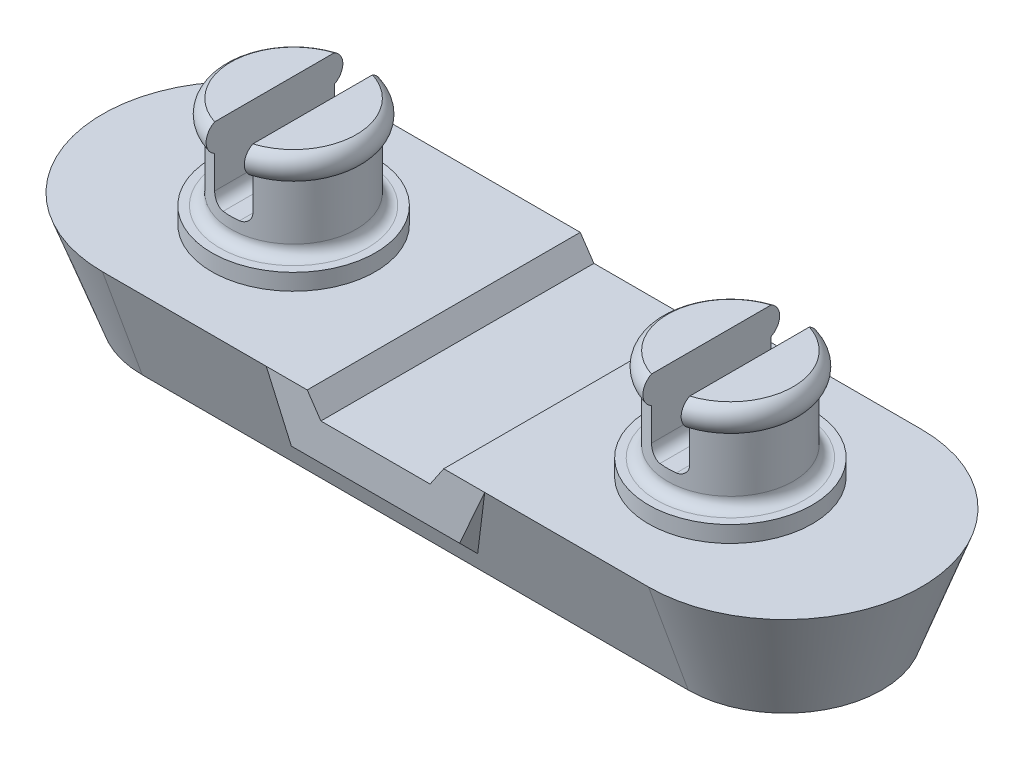
SolidWorks part; units mm, degrees
ref_plane "Front Plane" through (0, 0, 0) normal (0, 0, 1) x (1, 0, 0)
ref_plane "Top Plane" through (0, 0, 0) normal (0, 1, 0) x (1, 0, 0)
ref_plane "Right Plane" through (0, 0, 0) normal (1, 0, 0) x (0, 0, -1)
sketch "Sketch1" plane through (0, 0, 0) normal (0, 1, 0) x (1, 0, 0)
  line L0 (-10, 0) -> (10, 0) construction
  line L1 (-10, 5) -> (10, 5)
  line L2 (-10, -5) -> (10, -5)
  arc A0 (-10, 5) -> (-10, -5) centre (-10, 0) ccw
  arc A1 (10, -5) -> (10, 5) centre (10, 0) ccw
  point P3 (0, 0)
  point P8 (0, 0)
  point P9 (0, 0)
  dimension "D1" = 20
  dimension "D2" = 10
extrude "Boss-Extrude1" add sketch "Sketch1" against normal blind 4 draft 20
sketch "Sketch2" plane through (0, 0, 0) normal (0, 0, 1) x (1, 0, 0)
  line L0 (-8, 4.4068) -> (-8, 0) construction
  line L1 (-5, 0) -> (-8, 0)
  line L2 (-10, 0) -> (10, 0) construction
  line L3 (-5, 0) -> (-5, 0.6)
  line L4 (-5.7, 4) -> (-8, 4)
  line L5 (-8, 0) -> (-8, 4)
  line L6 (-5, 0.6) -> (-5.7, 0.6)
  line L7 (-5.7, 0.6) -> (-5.7, 3)
  arc A0 (-5.7, 3) -> (-5.7, 4) centre (-5.9667, 3.5) ccw
  point P3 (-7.1372, 1.7401)
  point P9 (-6.744, 1.5533)
  point P15 (-6.7109, 2.1828)
  point P16 (-5, 0.3)
  point P17 (-5.4, 3.5)
  point P18 (-7.6895, 4)
  point P19 (-8, 4.4068)
  dimension "D1" = 2.3
  dimension "D2" = 3
  dimension "D3" = 0.6
  dimension "D4" = 3
  dimension "D5" = 2.6
  dimension "D6" = 4
  dimension "D7" = 8
revolve "Revolve1" add sketch "Sketch2" angle 360 about L0
sketch "Sketch3" plane through (0, 0, 0) normal (0, 0, 1) x (1, 0, 0)
  line L1 (-8.7, 1.4068) -> (-7.3, 1.4068)
  line L2 (-8.7, 1.4068) -> (-8.7, 7.4068)
  line L3 (-8.7, 7.4068) -> (-7.3, 7.4068)
  line L4 (-7.3, 1.4068) -> (-7.3, 7.4068)
  line L5 (-8.7, 1.4068) -> (-7.3, 7.4068) construction
  line L6 (-8.7, 7.4068) -> (-7.3, 1.4068) construction
  point P0 (-8, 4.4068)
  dimension "D1" = 1.4
  dimension "D2" = 6
extrude "Cut-Extrude1" cut sketch "Sketch3" against normal through all both and the other way through all
fillet "Fillet1" radius 0.4 3 edges at (-10.3, 0.6, 0) (-7.3, 1.4068, 0) (-8.7, 1.4068, 0)
mirror "Mirror1" about plane through (0, 0, 0) normal (1, 0, 0) of "Fillet1", "Cut-Extrude1", "Revolve1"
sketch "Sketch4" plane through (0, 0, 0) normal (0, 0, 1) x (1, 0, 0)
  line L0 (-4, 0) -> (4, 0)
  line L1 (4, 0) -> (3.1142, -2)
  line L2 (3.1142, -2) -> (-3.1142, -2)
  line L3 (-3.1142, -2) -> (-4, 0)
  point P3 (0, 0)
  dimension "D1" = 8
  dimension "D2" = 2
extrude "Boss-Extrude2" add sketch "Sketch4" along normal mid plane 10
chamfer "Chamfer1" distance 0.8 angle 45 2 edges at (0, -2, 4.2721) (0, -2, -4.2721) first distance on face at (0, -2, 4.636) first distance on face at (0, -2, -4.636)
sketch "Sketch5" plane through (0, 0, 0) normal (0, 0, 1) x (1, 0, 0)
  line L0 (-2.5, 0) -> (2.5, 0)
  line L1 (2.5, 0) -> (2, -0.7357)
  line L2 (2, -0.7357) -> (-2, -0.7357)
  line L3 (-2, -0.7357) -> (-2.5, 0)
  point P3 (0, 0)
  point P6 (-2.7291, -0.7357)
  point P7 (-3.1984, 0)
  dimension "D1" = 4
  dimension "D2" = 5
extrude "Cut-Extrude2" cut sketch "Sketch5" against normal through all both and the other way through all
